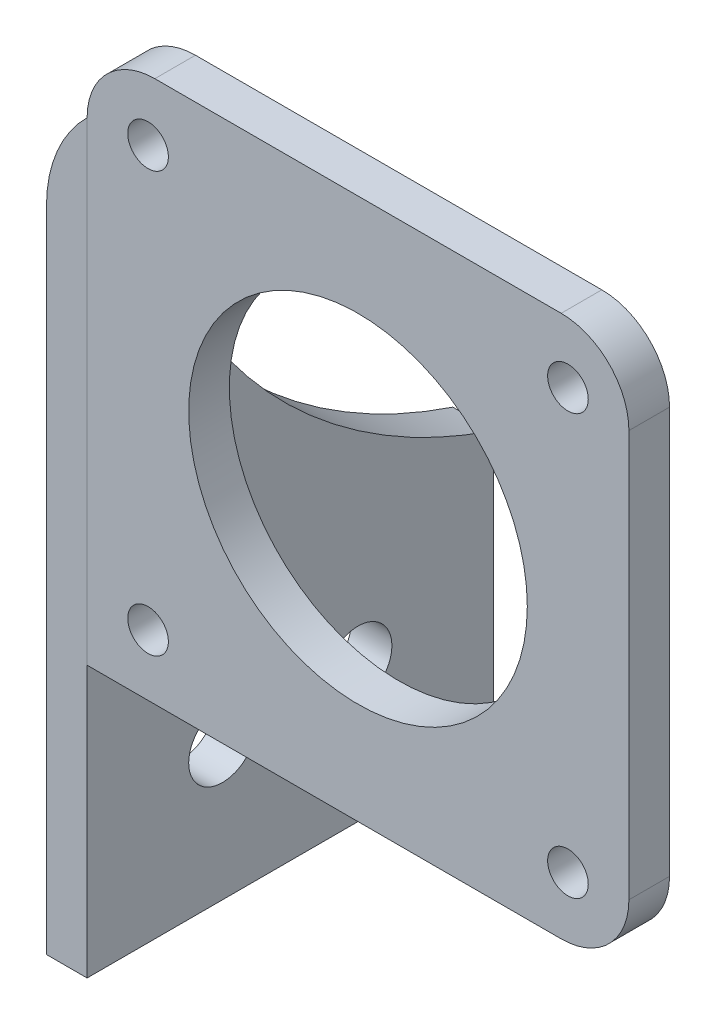
SolidWorks part; units mm, degrees
ref_plane "Front Plane" through (0, 0, 0) normal (0, 0, 1) x (1, 0, 0)
ref_plane "Top Plane" through (0, 0, 0) normal (0, 1, 0) x (1, 0, 0)
ref_plane "Right Plane" through (0, 0, 0) normal (1, 0, 0) x (0, 0, -1)
sketch "Sketch1" plane through (0, 0, 0) normal (0, 0, 1) x (1, 0, 0)
  line L0 (-15.5, 15.5) -> (15.5, 15.5) construction
  line L1 (-15, -20) -> (15, -20)
  line L2 (-20, -15) -> (-20, 15)
  line L3 (-15, 20) -> (15, 20)
  line L4 (20, -15) -> (20, 15)
  line L5 (-20, -20) -> (20, 20) construction
  line L6 (-20, 20) -> (20, -20) construction
  line L7 (-15.5, 15.5) -> (-15.5, -15.5) construction
  line L8 (-15.5, -15.5) -> (15.5, -15.5) construction
  line L9 (-20, -15) -> (-20, -20)
  line L10 (-20, -20) -> (-15, -20)
  circle A0 centre (0, 0) radius 12.5
  circle A1 centre (-15.5, 15.5) radius 1.5
  circle A2 centre (15.5, 15.5) radius 1.5
  circle A3 centre (-15.5, -15.5) radius 1.5
  circle A4 centre (15.5, -15.5) radius 1.5
  arc A5 (15, -20) -> (20, -15) centre (15, -15) ccw
  arc A6 (15, 20) -> (20, 15) centre (15, 15) cw
  arc A7 (-20, 15) -> (-15, 20) centre (-15, 15) cw
  point P0 (0, 0)
  dimension "D2" = 25
  dimension "D3" = 3
  dimension "D4" = 3
  dimension "D6" = 3
  dimension "D7" = 3
  dimension "D8" = 5
  dimension "D1" = 40
  dimension "D5" = 31
extrude "Boss-Extrude1" add sketch "Sketch1" along normal blind 3
ref_plane "Plane1" through (-20, 0, 0) normal (-1, 0, 0) x (0, 0, 1)
sketch "Sketch2" plane through (-20, 0, 0) normal (-1, 0, 0) x (0, 0, 1)
  line L1 (3, -40) -> (-27, -40)
  line L2 (-27, -40) -> (-27, -20)
  line L4 (-17, -20) -> (-17, -40) construction
  line L5 (-7, -20) -> (-7, -40) construction
  line L6 (-27, -30) -> (3, -30) construction
  line L17 (3, -40) -> (3, 15)
  line L18 (3, 15) -> (0, 15)
  arc A0 (0, 15) -> (-27, -20) centre (-39.533, 17.5826) cw
  circle A1 centre (-17, -30) radius 2.5
  circle A2 centre (-7, -30) radius 2.5
  dimension "D5" = 39.6172
  dimension "D7" = 5
  dimension "D8" = 5
  dimension "D1" = 55
  dimension "D2" = 30
  dimension "D3" = 10
  dimension "D4" = 10
  dimension "D6" = 20
extrude "Boss-Extrude2" add sketch "Sketch2" along normal blind 3 separate body
fillet "Fillet1" radius 10 1 edges at (-23, 15, 1.5)
ref_plane "Plane2" through (-20, -20, 0) normal (0, -1, 0) x (-1, 0, 0)
